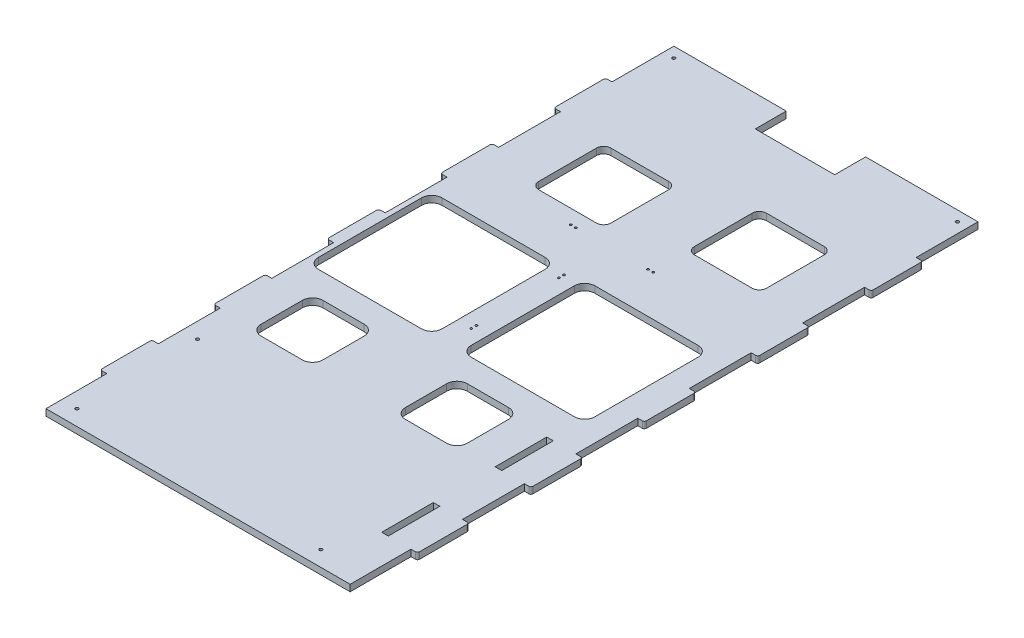
SolidWorks part; units mm, degrees
material "Beech"
ref_plane "Front Plane" through (0, 0, 0) normal (0, 0, 1) x (1, 0, 0)
ref_plane "Top Plane" through (0, 0, 0) normal (0, 1, 0) x (1, 0, 0)
ref_plane "Right Plane" through (0, 0, 0) normal (1, 0, 0) x (0, 0, -1)
sketch "Sketch1" plane through (0, 0, 0) normal (0, 1, 0) x (1, 0, 0)
  line L1 (0, 0) -> (295, 0)
  line L2 (0, 0) -> (0, 59)
  line L3 (0, 609) -> (295, 609)
  line L4 (295, 0) -> (295, 59)
  line L5 (0, 59) -> (-6.35, 59)
  line L7 (0, 109) -> (-6.35, 109)
  line L8 (-6.35, 59) -> (-6.35, 109)
  line L9 (0, 169) -> (-6.35, 169)
  line L10 (-6.35, 169) -> (-6.35, 219)
  line L11 (0, 219) -> (-6.35, 219)
  line L13 (0, 279) -> (-6.35, 279)
  line L14 (-6.35, 279) -> (-6.35, 329)
  line L15 (0, 329) -> (-6.35, 329)
  line L17 (0, 389) -> (-6.35, 389)
  line L18 (-6.35, 389) -> (-6.35, 439)
  line L19 (0, 439) -> (-6.35, 439)
  line L21 (0, 499) -> (-6.35, 499)
  line L22 (-6.35, 499) -> (-6.35, 549)
  line L23 (0, 549) -> (-6.35, 549)
  line L25 (295, 59) -> (301.35, 59)
  line L27 (295, 109) -> (301.35, 109)
  line L28 (301.35, 59) -> (301.35, 109)
  line L29 (295, 169) -> (301.35, 169)
  line L30 (301.35, 169) -> (301.35, 219)
  line L31 (295, 219) -> (301.35, 219)
  line L33 (295, 279) -> (301.35, 279)
  line L34 (301.35, 279) -> (301.35, 329)
  line L35 (295, 329) -> (301.35, 329)
  line L37 (295, 389) -> (301.35, 389)
  line L38 (301.35, 389) -> (301.35, 439)
  line L39 (295, 439) -> (301.35, 439)
  line L41 (295, 499) -> (301.35, 499)
  line L42 (301.35, 499) -> (301.35, 549)
  line L43 (295, 549) -> (301.35, 549)
  line L44 (0, 549) -> (0, 609)
  line L46 (0, 329) -> (0, 389)
  line L49 (0, 219) -> (0, 279)
  line L50 (0, 109) -> (0, 169)
  line L51 (295, 109) -> (295, 169)
  line L52 (295, 219) -> (295, 279)
  line L53 (295, 329) -> (295, 389)
  line L54 (295, 439) -> (295, 499)
  line L55 (295, 549) -> (295, 609)
  line L56 (0, 439) -> (0, 499)
  dimension "D1" = 609
  dimension "D2" = 295
  dimension "D3" = 6.35
  dimension "D4" = 50
  dimension "D5" = 59
  dimension "D7" = 60
  dimension "D8" = 50
  dimension "D9" = 6.35
  dimension "D11" = 59
  dimension "D12" = 60
  dimension "D6" = 5
  dimension "D10" = 5
extrude "Boss-Extrude1" add sketch "Sketch1" along normal blind 6.35
fillet "Fillet1" radius 2 20 edges at (301.35, 3.175, -549) (301.35, 3.175, -499) (301.35, 3.175, -439) (301.35, 3.175, -389) (301.35, 3.175, -329) (301.35, 3.175, -279) (301.35, 3.175, -219) (301.35, 3.175, -169) (301.35, 3.175, -109) (301.35, 3.175, -59) (-6.35, 3.175, -59) (-6.35, 3.175, -109) (-6.35, 3.175, -169) (-6.35, 3.175, -219) (-6.35, 3.175, -279) (-6.35, 3.175, -329) (-6.35, 3.175, -389) (-6.35, 3.175, -439) (-6.35, 3.175, -499) (-6.35, 3.175, -549)
sketch "Sketch2" plane through (0, 6.35, 0) normal (0, 1, 0) x (1, 0, 0)
  line L0 (266.65, 0) -> (266.65, 100) construction
  line L1 (0, 0) -> (295, 0) construction
  line L2 (0, 609) -> (0, 0) construction
  line L3 (295, 609) -> (295, 0) construction
  line L4 (0, 150) -> (266.65, 100) construction
  line L5 (266.65, 169) -> (266.65, 219)
  line L6 (266.65, 59) -> (273, 59)
  line L7 (266.65, 59) -> (266.65, 109)
  line L8 (266.65, 109) -> (273, 109)
  line L9 (273, 59) -> (273, 109)
  line L10 (266.65, 169) -> (273, 169)
  line L11 (273, 169) -> (273, 219)
  line L12 (266.65, 219) -> (273, 219)
  line L13 (0, 84.2124) -> (266.65, 84) construction
  line L14 (55.0424, 492.8768) -> (111.0424, 492.8768)
  line L15 (48.0424, 485.8768) -> (48.0424, 429.8768)
  line L16 (55.0424, 422.8768) -> (111.0424, 422.8768)
  line L17 (118.0424, 485.8768) -> (118.0424, 429.8768)
  line L18 (185.2335, 513.6581) -> (241.2335, 513.6581)
  line L19 (178.2335, 506.6581) -> (178.2335, 450.6581)
  line L20 (185.2335, 443.6581) -> (241.2335, 443.6581)
  line L21 (248.2335, 506.6581) -> (248.2335, 450.6581)
  line L22 (43.325, 225.298) -> (83.325, 225.298)
  line L23 (33.325, 215.298) -> (33.325, 175.298)
  line L24 (43.325, 165.298) -> (83.325, 165.298)
  line L25 (93.325, 215.298) -> (93.325, 175.298)
  line L26 (33.325, 225.298) -> (93.325, 165.298) construction
  line L27 (33.325, 165.298) -> (93.325, 225.298) construction
  line L32 (133.325, 0) -> (133.325, 609) construction
  line L33 (295, 609) -> (0, 609) construction
  line L34 (5, 369.1536) -> (125, 369.1536)
  line L35 (5, 369.1536) -> (5, 249.1536)
  line L36 (5, 249.1536) -> (125, 249.1536)
  line L37 (125, 369.1536) -> (125, 249.1536)
  line L38 (153, 369.4528) -> (273, 369.4528)
  line L39 (153, 369.4528) -> (153, 249.4528)
  line L40 (153, 249.4528) -> (273, 249.4528)
  line L41 (273, 369.4528) -> (273, 249.4528)
  line L42 (233.325, 165.298) -> (173.325, 225.298) construction
  line L43 (233.325, 225.298) -> (173.325, 165.298) construction
  line L44 (173.325, 215.298) -> (173.325, 175.298)
  line L45 (223.325, 165.298) -> (183.325, 165.298)
  line L46 (233.325, 215.298) -> (233.325, 175.298)
  line L47 (223.325, 225.298) -> (183.325, 225.298)
  line L48 (100, 150.298) -> (105, 150.298) construction
  line L49 (105, 150.298) -> (165, 150.298) construction
  line L50 (165, 150.298) -> (170, 150.298) construction
  line L51 (147.5, 609) -> (147.5, 0) construction
  line L52 (109, 609) -> (186, 609)
  line L53 (109, 609) -> (109, 579)
  line L54 (109, 579) -> (186, 579)
  line L55 (186, 609) -> (186, 579)
  line L56 (147.5, 609) -> (147.5, 579) construction
  line L57 (100, 409) -> (180, 409) construction
  line L58 (180, 409) -> (175, 409) construction
  line L59 (175, 409) -> (105, 409) construction
  line L60 (105, 409) -> (100, 409) construction
  arc A0 (48.0424, 429.8768) -> (55.0424, 422.8768) centre (55.0424, 429.8768) ccw
  arc A1 (111.0424, 422.8768) -> (118.0424, 429.8768) centre (111.0424, 429.8768) ccw
  arc A2 (111.0424, 492.8768) -> (118.0424, 485.8768) centre (111.0424, 485.8768) cw
  arc A3 (55.0424, 492.8768) -> (48.0424, 485.8768) centre (55.0424, 485.8768) ccw
  arc A4 (178.2335, 450.6581) -> (185.2335, 443.6581) centre (185.2335, 450.6581) ccw
  arc A5 (241.2335, 443.6581) -> (248.2335, 450.6581) centre (241.2335, 450.6581) ccw
  arc A6 (241.2335, 513.6581) -> (248.2335, 506.6581) centre (241.2335, 506.6581) cw
  arc A7 (185.2335, 513.6581) -> (178.2335, 506.6581) centre (185.2335, 506.6581) ccw
  arc A8 (33.325, 175.298) -> (43.325, 165.298) centre (43.325, 175.298) ccw
  arc A9 (83.325, 165.298) -> (93.325, 175.298) centre (83.325, 175.298) ccw
  arc A10 (83.325, 225.298) -> (93.325, 215.298) centre (83.325, 215.298) cw
  arc A11 (43.325, 225.298) -> (33.325, 215.298) centre (43.325, 215.298) ccw
  arc A16 (223.325, 225.298) -> (233.325, 215.298) centre (223.325, 215.298) cw
  arc A17 (183.325, 225.298) -> (173.325, 215.298) centre (183.325, 215.298) ccw
  arc A18 (183.325, 165.298) -> (173.325, 175.298) centre (183.325, 175.298) cw
  arc A19 (233.325, 175.298) -> (223.325, 165.298) centre (223.325, 175.298) cw
  circle A20 centre (15, 15) radius 1.5
  circle A21 centre (251.65, 15) radius 1.5
  circle A22 centre (15, 131.9259) radius 1.5
  circle A23 centre (10, 599) radius 1.5
  circle A24 centre (285, 599) radius 1.5
  circle A25 centre (100, 150.298) radius 1.025 construction
  circle A26 centre (105, 150.298) radius 1.025 construction
  circle A27 centre (165, 150.298) radius 1.025 construction
  circle A28 centre (170, 150.298) radius 1.025 construction
  circle A29 centre (100, 409) radius 1.025
  circle A30 centre (105, 409) radius 1.025
  circle A31 centre (175, 409) radius 1.025
  circle A32 centre (180, 409) radius 1.025
  circle A33 centre (138.8673, 363.5767) radius 1.025
  circle A34 centre (138.8673, 358.5767) radius 1.025
  circle A35 centre (138.8673, 278.5767) radius 1.025
  circle A36 centre (138.8673, 273.5767) radius 1.025
  point P33 (118.0424, 422.8768)
  point P36 (118.0424, 492.8768)
  point P39 (48.0424, 492.8768)
  point P42 (178.2335, 443.6581)
  point P47 (248.2335, 513.6581)
  point P50 (178.2335, 513.6581)
  point P51 (63.325, 195.298)
  point P74 (133.325, 84.1062)
  point P99 (203.325, 195.298)
  dimension "D10" = 7
  dimension "D11" = 7
  dimension "D16" = 10
  dimension "D17" = 70
  dimension "D22" = 3
  dimension "D25" = 3
  dimension "D28" = 3
  dimension "D18" = 3
  dimension "D31" = 3
  dimension "D40" = 2.05
  dimension "D42" = 2.05
  dimension "D43" = 2.05
  dimension "D44" = 2.05
  dimension "D49" = 2.05
  dimension "D50" = 2.05
  dimension "D51" = 2.05
  dimension "D52" = 2.05
  dimension "D58" = 2.05
  dimension "D59" = 2.05
  dimension "D60" = 2.05
  dimension "D61" = 2.05
  dimension "D1" = 100
  dimension "D2" = 150
  dimension "D3" = 6.35
  dimension "D4" = 50
  dimension "D6" = 70
  dimension "D7" = 70
  dimension "D8" = 70
  dimension "D9" = 70
  dimension "D12" = 60
  dimension "D13" = 60
  dimension "D14" = 22
  dimension "D15" = 59
  dimension "12" = 120
  dimension "D19" = 120
  dimension "D20" = 120
  dimension "D21" = 120
  dimension "D23" = 15
  dimension "D24" = 15
  dimension "D26" = 15
  dimension "D27" = 15
  dimension "D29" = 15
  dimension "D30" = 15
  dimension "D32" = 10
  dimension "D33" = 10
  dimension "D34" = 10
  dimension "D35" = 10
  dimension "D36" = 5
  dimension "D37" = 22
  dimension "D38" = 15
  dimension "D39" = 200
  dimension "D41" = 5
  dimension "D45" = 5
  dimension "D46" = 60
  dimension "D47" = 30
  dimension "D48" = 77
  dimension "D53" = 5
  dimension "D54" = 5
  dimension "D55" = 70
  dimension "D56" = 200
  dimension "D57" = 200
  dimension "D62" = 5
  dimension "D63" = 5
  dimension "D64" = 80
  dimension "D5" = 2
extrude "Cut-Extrude1" cut sketch "Sketch2" against normal blind 6.35
fillet "Fillet2" radius 10 8 edges at (125, 3.175, -249.1536) (5, 3.175, -249.1536) (5, 3.175, -369.1536) (125, 3.175, -369.1536) (153, 3.175, -249.4528) (273, 3.175, -249.4528) (273, 3.175, -369.4528) (153, 3.175, -369.4528)
